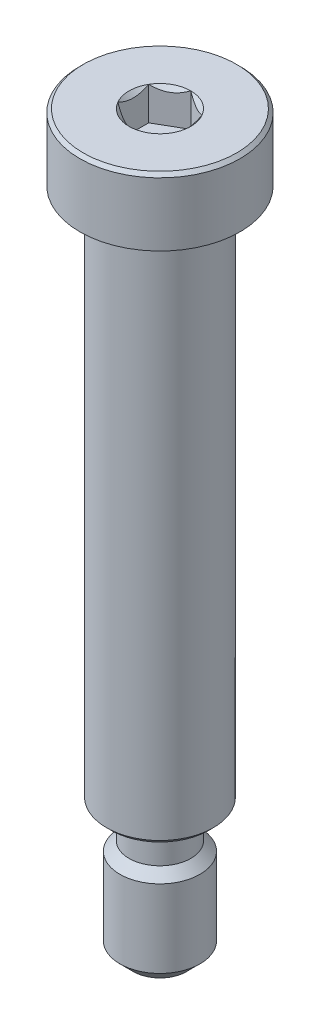
SolidWorks part; units mm, degrees
ref_plane "Front" through (0, 0, 0) normal (0, 0, 1) x (1, 0, 0)
ref_plane "Top" through (0, 0, 0) normal (0, 1, 0) x (1, 0, 0)
ref_plane "Right" through (0, 0, 0) normal (1, 0, 0) x (0, 0, -1)
sketch "Sketch1" plane through (0, 0, 0) normal (0, 1, 0) x (1, 0, 0)
  circle A0 centre (0, 0) radius 9.525
  point P3 (0, -9.525)
  dimension "Head Dia" = 19.05
extrude "Extrude1" add sketch "Sketch1" along normal blind 7.9375
sketch "Sketch2" plane through (0, 7.9375, 0) normal (0, 1, 0) x (-1, 0, 0)
  line L1 (0, -3.6662) -> (3.175, -1.8331)
  line L2 (3.175, -1.8331) -> (3.175, 1.8331)
  line L3 (3.175, 1.8331) -> (0, 3.6662)
  line L4 (0, 3.6662) -> (-3.175, 1.8331)
  line L5 (-3.175, 1.8331) -> (-3.175, -1.8331)
  line L6 (-3.175, -1.8331) -> (0, -3.6662)
  circle A0 centre (0, 0) radius 3.175 construction
  circle A1 centre (0, 0) radius 9.525 construction
  dimension "Hex Key" = 6.35
extrude "Cut-Extrude1" cut sketch "Sketch2" against normal blind 3.9688
sketch "Sketch18" plane through (0, 7.9375, 0) normal (0, 1, 0) x (1, 0, 0)
  circle A0 centre (0, 0) radius 3.6662
extrude "Cut-Extrude4" cut sketch "Sketch18" against normal blind 1.3229 draft 45
ref_plane "Plane2" through (0, -63.5, 0) normal (0, -1, 0) x (1, 0, 0)
sketch "Sketch4" plane through (0, -63.5, 0) normal (0, -1, 0) x (1, 0, 0)
  circle A0 centre (0, 0) radius 6.35
  circle A1 centre (0, 0) radius 9.525 construction
  dimension "Shoulder Dia" = 12.7
extrude "Extrude2" add sketch "Sketch4" against normal blind 63.5
sketch "Sketch5" plane through (0, -63.5, 0) normal (0, -1, 0) x (1, 0, 0)
  circle A0 centre (0, 0) radius 4.7625
  circle A2 centre (0, 0) radius 6.35 construction
  dimension "Thread Dia" = 9.525
extrude "Extrude3" add sketch "Sketch5" along normal blind 15.875
sketch "Sketch16" plane through (0, 0, 0) normal (1, 0, 0) x (0, 0, -1)
  line L0 (-4.7625, -79.375) -> (4.7625, -79.375) construction
  line L2 (-4.7625, -63.5) -> (-4.7625, -79.375) construction
  point P0 (-4.7625, -73.4219)
  dimension "D1" = 5.9531
chamfer "Chamfer1" distance 1.5875 angle 45 1 edges at (0, -79.375, -4.7625)
sketch "Sketch12" plane through (0, -79.375, 0) normal (0, -1, 0) x (1, 0, 0)
  circle A0 centre (0, 0) radius 4.7625
  circle A1 centre (0, 0) radius 4.7625 construction
curve "Helix/Spiral1" pitch 1.5875 height 15.0812 turns 9.5 parameters "Thread Pitch "=1.5875
sketch "Sketch13" plane through (0, 0, 0) normal (0, 0, 1) x (1, 0, 0)
  line L0 (4.7625, -79.375) -> (4.7625, -80.7641)
  line L1 (4.7625, -80.7641) -> (3.7314, -80.1688)
  line L2 (3.7314, -80.1688) -> (3.7314, -79.9703)
  line L3 (3.7314, -79.9703) -> (4.7625, -79.375)
  line L4 (4.7625, -80.0695) -> (3.7314, -80.0695) construction
  line L6 (4.2469, -79.6727) -> (4.2469, -80.4664) construction
  line L7 (-3.175, -79.375) -> (3.175, -79.375) construction
  line L8 (4.7625, -77.7875) -> (4.7625, -63.5) construction
  dimension "D1" = 60
  dimension "D2" = 0.1984
  dimension "D3" = 0.7937
sweep "Cut-Sweep1" [suppressed] cut profiles "Sketch13" path "Helix/Spiral1"
sketch "Sketch17" plane through (0, 0, 0) normal (0, 0, 1) x (1, 0, 0)
  line L0 (-6.35, -63.5) -> (6.35, -63.5) construction
  line L1 (0, 0) -> (0, -63.5) construction
  line L2 (4.8628, -63.5) -> (6.35, -63.5)
  line L3 (6.35, -67.4688) -> (6.35, -63.5)
  line L4 (6.35, -63.5) -> (0, -63.5) construction
  line L5 (3.6722, -64.6906) -> (3.6722, -67.4688)
  line L6 (3.6722, -67.4688) -> (6.35, -67.4688) construction
  line L7 (3.6722, -67.4688) -> (6.35, -70.1466)
  line L8 (6.35, -70.1466) -> (6.35, -67.4688)
  line L9 (3.7314, -80.1688) -> (3.7314, -79.9703) construction
  arc A0 (4.8628, -63.5) -> (3.6722, -64.6906) centre (4.8628, -64.6906) ccw
  point P14 (3.6722, -63.5)
  dimension "D1" = 0.0592
revolve "Cut-Revolve1" cut sketch "Sketch17" angle 360 about L1
chamfer "Chamfer2" distance 0.5292 angle 45 1 edges at (0, -63.5, -6.35)
ref_plane "Plane1" through (0, 7.5406, 0) normal (0, 1, 0) x (-1, 0, 0)
sketch "Sketch10" plane through (0, 7.5406, 0) normal (0, 1, 0) x (-1, 0, 0)
  line L0 (0, 0) -> (-9.0495, 0) construction
  line L1 (0, 0) -> (-9.5119, -0.4985) construction
  line L2 (-9.5119, -0.4985) -> (-9.6514, -0.5058)
  line L3 (-9.5119, -0.4985) -> (-9.075, -0.0616)
  line L4 (0, 0) -> (-9.5119, 0.4985) construction
  line L5 (-9.075, 0.0616) -> (-9.5119, 0.4985)
  line L6 (-9.6514, -0.5058) -> (-9.6514, 0.5058)
  line L7 (-9.6514, 0.5058) -> (-9.5119, 0.4985)
  circle A0 centre (0, 0) radius 9.525 construction
  arc A2 (-9.075, -0.0616) -> (-9.075, 0.0616) centre (-9.1366, 0) ccw
  point P3 (-9.525, 0)
  dimension "D4" = 0.0871
  dimension "D1" = 90
  dimension "D2" = 6
  dimension "D3" = 0.1395
extrude "Cut-Extrude3" [suppressed] cut sketch "Sketch10" against normal blind 5.2917
pattern_circular "CirPattern2" [suppressed] count 60 over 360
chamfer "Chamfer3" distance 0.3969 angle 45 1 edges at (0, 7.9375, 9.525)
sketch "Sketch14" [suppressed] plane through (0, 7.9375, 0) normal (0, 1, 0) x (1, 0, 0)
  circle A0 centre (0, 0) radius 9.525
  arc A1 (-5.9943, -7.4023) -> (-5.1877, -7.9883) centre (0, 0) ccw construction
sketch "Sketch15" plane through (0, 0, 0) normal (1, 0, 0) x (0, 0, -1)
  line L0 (-4.7625, 0) -> (-4.7625, -79.375)
  line L1 (4.7625, -79.375) -> (4.7625, 0)
equation "\"D1@Cut-Extrude1\"=\"Head Ht@Extrude1\"/2"
equation "\"D1@Cut-Extrude3\"=\"Head Ht@Extrude1\"*2/3"
equation "\"D1@Chamfer1\" = \"Thread Length@Extrude3\" * .1"
equation "\"D3@Helix/Spiral1\" = \"Thread Length@Extrude3\" -  ( \"Thread Pitch @Helix/Spiral1\" * .5 ) "
equation "\"D2@Sketch13\" = \"Thread Pitch @Helix/Spiral1\" * .125"
equation "\"D3@Sketch13\" = \"Thread Pitch @Helix/Spiral1\" * .5"
equation "\"D3@Sketch10\" = \"Head Dia@Sketch1\" * .0073205143"
equation "\"D4@Sketch10\" = \"Head Dia@Sketch1\" * .0045714286"
equation "\"D1@Sketch16\" = \"Thread Pitch @Helix/Spiral1\"*3.750"
equation "\"D1@Chamfer2\" = \"Thread Pitch @Helix/Spiral1\"/3"
equation "\"D1@Plane1\" = \"Head Ht@Extrude1\"/20"
equation "\"D1@Chamfer3\" = \"Head Ht@Extrude1\"/20"
equation "\"D1@Cut-Extrude4\" = \"D1@Cut-Extrude1\"/3"
equation "\"Thread Neck Width@Sketch17\" = \"Thread Length@Extrude3\" * .25"
equation "\"Thread Neck Fillet@Sketch17\" = \"Thread Neck Width@Sketch17\" * .3"
